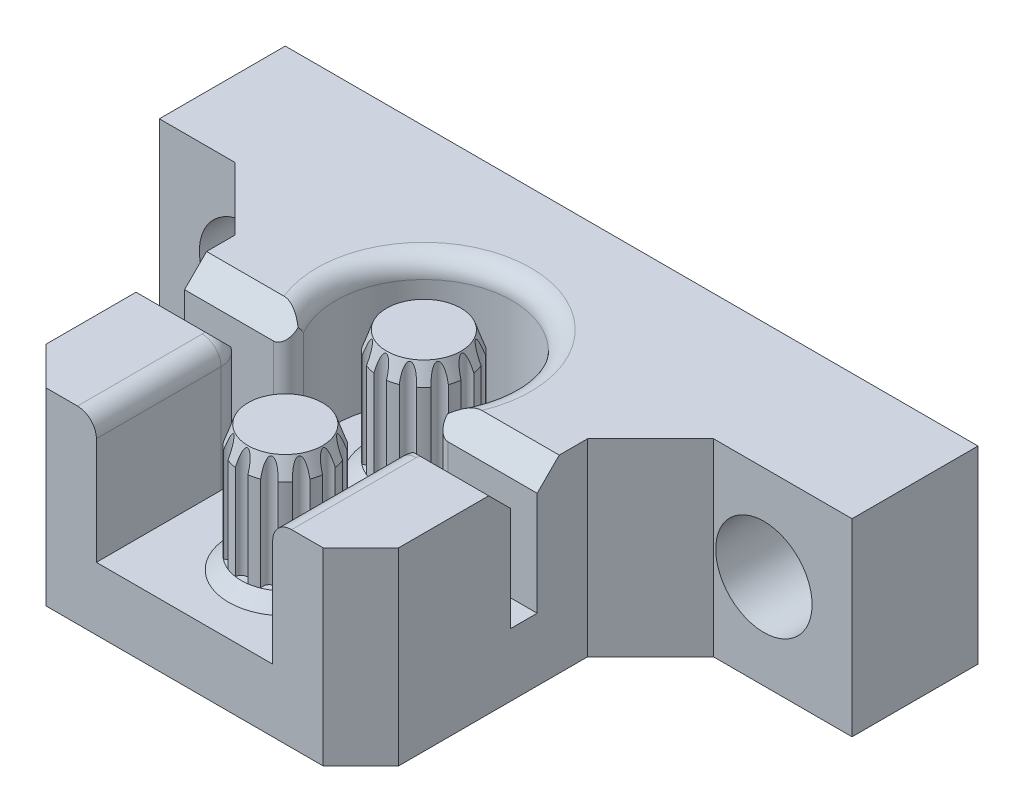
SolidWorks part; units mm, degrees
ref_plane "Front Plane" through (0, 0, 0) normal (0, 0, 1) x (1, 0, 0)
ref_plane "Top Plane" through (0, 0, 0) normal (0, 1, 0) x (1, 0, 0)
ref_plane "Right Plane" through (0, 0, 0) normal (1, 0, 0) x (0, 0, -1)
sketch "Sketch1" plane through (0, 0, 0) normal (0, 1, 0) x (1, 0, 0)
  line L0 (491.0807, 689.6451) -> (480.0807, 689.6451)
  line L1 (535.0807, 689.6451) -> (519.0807, 689.6451)
  line L2 (535.0807, 689.6451) -> (535.0807, 699.6451)
  line L3 (535.0807, 699.6451) -> (480.0807, 699.6451)
  line L4 (480.0807, 689.6451) -> (480.0807, 699.6451)
  line L6 (491.0807, 689.6451) -> (491.0807, 666.6451)
  line L7 (491.0807, 666.6451) -> (519.0807, 666.6451)
  line L8 (519.0807, 689.6451) -> (519.0807, 666.6451)
  dimension "D1" = 10
  dimension "D2" = 55
  dimension "D3" = 11
  dimension "D4" = 16
  dimension "D5" = 23
  dimension "D6" = 28
extrude "Boss-Extrude1" add sketch "Sketch1" along normal blind 15
sketch "Sketch4" plane through (0, 0, -699.6451) normal (0, 0, -1) x (-1, 0, 0)
  line L0 (-480.0807, 15) -> (-480.0807, 0) construction
  circle A0 centre (-487.0807, 7.5) radius 1.85
  circle A1 centre (-528.0807, 7.5) radius 1.85
  point P9 (-480.0807, 7.5)
  dimension "D1" = 3.7
  dimension "D2" = 41
  dimension "D3" = 7
extrude "Cut-Extrude1" cut sketch "Sketch4" against normal blind 16
sketch "Sketch5" plane through (0, 0, -689.6451) normal (0, 0, 1) x (1, 0, 0)
  circle A0 centre (487.0807, 7.5) radius 3.825
  circle A1 centre (528.0807, 7.5) radius 3.825
  dimension "D1" = 7.65
extrude "Cut-Extrude2" cut sketch "Sketch5" against normal blind 6
sketch "Sketch6" plane through (0, 15, 0) normal (0, 1, 0) x (1, 0, 0)
  line L0 (519.0807, 689.6451) -> (535.0807, 689.6451) construction
  line L1 (491.0807, 689.6451) -> (491.0807, 666.6451) construction
  line L2 (491.0807, 680.6451) -> (500.1817, 680.6451)
  line L4 (519.0807, 680.6451) -> (519.0807, 678.5451)
  line L5 (519.0807, 678.5451) -> (512.0807, 678.5451)
  line L6 (512.0807, 678.5451) -> (512.0807, 666.6451)
  line L7 (491.0807, 666.6451) -> (519.0807, 666.6451) construction
  line L8 (512.0807, 666.6451) -> (498.0807, 666.6451)
  line L9 (498.0807, 666.6451) -> (498.0807, 678.5451)
  line L10 (498.0807, 678.5451) -> (491.0807, 678.5451)
  line L11 (491.0807, 678.5451) -> (491.0807, 680.6451)
  line L14 (519.0807, 666.6451) -> (519.0807, 689.6451) construction
  line L15 (509.9797, 680.6451) -> (519.0807, 680.6451)
  line L16 (535.0807, 699.6451) -> (480.0807, 699.6451) construction
  circle A0 centre (505.0807, 685.6451) radius 3.5
  arc A1 (509.9797, 680.6451) -> (500.1817, 680.6451) centre (505.0807, 685.6451) ccw
  circle A2 centre (506.0807, 673.6451) radius 3.5
  dimension "D1" = 2.1
  dimension "D7" = 7
  dimension "D3" = 7
  dimension "D2" = 7
  dimension "D4" = 9
  dimension "D5" = 14
  dimension "D6" = 14
  dimension "D8" = 12
  dimension "D9" = 1
extrude "Cut-Extrude3" cut sketch "Sketch6" against normal blind 10
chamfer "Chamfer1" distance 1 angle 45 2 edges at (506.0807, 5, -670.1451) (505.0807, 5, -682.1451)
chamfer "Chamfer2" distance 1.5 angle 20 2 edges at (506.0807, 15, -670.1451) (505.0807, 15, -682.1451) first distance on face at (506.0807, 6, -670.1451) first distance on face at (505.0807, 6, -682.1451)
fillet "Fillet1" radius 1 2 edges at (509.9797, 10, -680.6451) (500.1817, 10, -680.6451)
fillet "Fillet2" radius 2 2 edges at (512.0807, 10, -678.5451) (498.0807, 10, -678.5451)
chamfer "Chamfer3" distance 1.75 angle 45 4 edges at (493.5807, 15, -678.5451) (516.5807, 15, -678.5451) (515.5448, 15, -680.6451) (494.6166, 15, -680.6451) tangent propagation no
chamfer "Chamfer4" distance 5 angle 45 2 edges at (519.0807, 7.5, -689.6451) (491.0807, 7.5, -689.6451)
chamfer "Chamfer5" distance 3 angle 45 2 edges at (519.0807, 7.5, -666.6451) (491.0807, 7.5, -666.6451)
fillet "Fillet3" radius 1.5 5 edges at (512.0846, 15, -676.6703) (498.0768, 15, -676.6703) (512.0807, 15, -671.5951) (498.0807, 15, -671.5951) (505.0807, 15, -692.6451)
sketch "Sketch8" plane through (0, 15, 0) normal (0, 1, 0) x (1, 0, 0)
  circle A0 centre (501.5807, 685.6451) radius 0.5
  circle A2 centre (502.0496, 687.3951) radius 0.5
  circle A3 centre (503.3307, 688.6762) radius 0.5
  circle A4 centre (505.0807, 689.1451) radius 0.5
  circle A5 centre (506.8307, 688.6762) radius 0.5
  circle A6 centre (508.1118, 687.3951) radius 0.5
  circle A7 centre (508.5807, 685.6451) radius 0.5
  circle A8 centre (508.1118, 683.8951) radius 0.5
  circle A9 centre (506.8307, 682.614) radius 0.5
  circle A10 centre (505.0807, 682.1451) radius 0.5
  circle A11 centre (503.3307, 682.614) radius 0.5
  circle A12 centre (502.0496, 683.8951) radius 0.5
  circle A13 centre (502.5807, 673.6451) radius 0.5
  circle A15 centre (503.0496, 675.3951) radius 0.5
  circle A16 centre (504.3307, 676.6762) radius 0.5
  circle A17 centre (506.0807, 677.1451) radius 0.5
  circle A18 centre (507.8307, 676.6762) radius 0.5
  circle A19 centre (509.1118, 675.3951) radius 0.5
  circle A20 centre (509.5807, 673.6451) radius 0.5
  circle A21 centre (509.1118, 671.8951) radius 0.5
  circle A22 centre (507.8307, 670.614) radius 0.5
  circle A23 centre (506.0807, 670.1451) radius 0.5
  circle A24 centre (504.3307, 670.614) radius 0.5
  circle A25 centre (503.0496, 671.8951) radius 0.5
  circle A26 centre (505.0807, 685.6451) radius 3.5 construction
  circle A27 centre (505.0807, 685.6451) radius 3.5 construction
  circle A28 centre (506.0807, 673.6451) radius 3.5 construction
  circle A29 centre (506.0807, 673.6451) radius 3.5 construction
  point P29 (505.0807, 685.6451)
  point P56 (506.0807, 673.6451)
  dimension "D1" = 12
  dimension "D2" = 12
extrude "Cut-Extrude4" cut sketch "Sketch8" against normal blind 9
